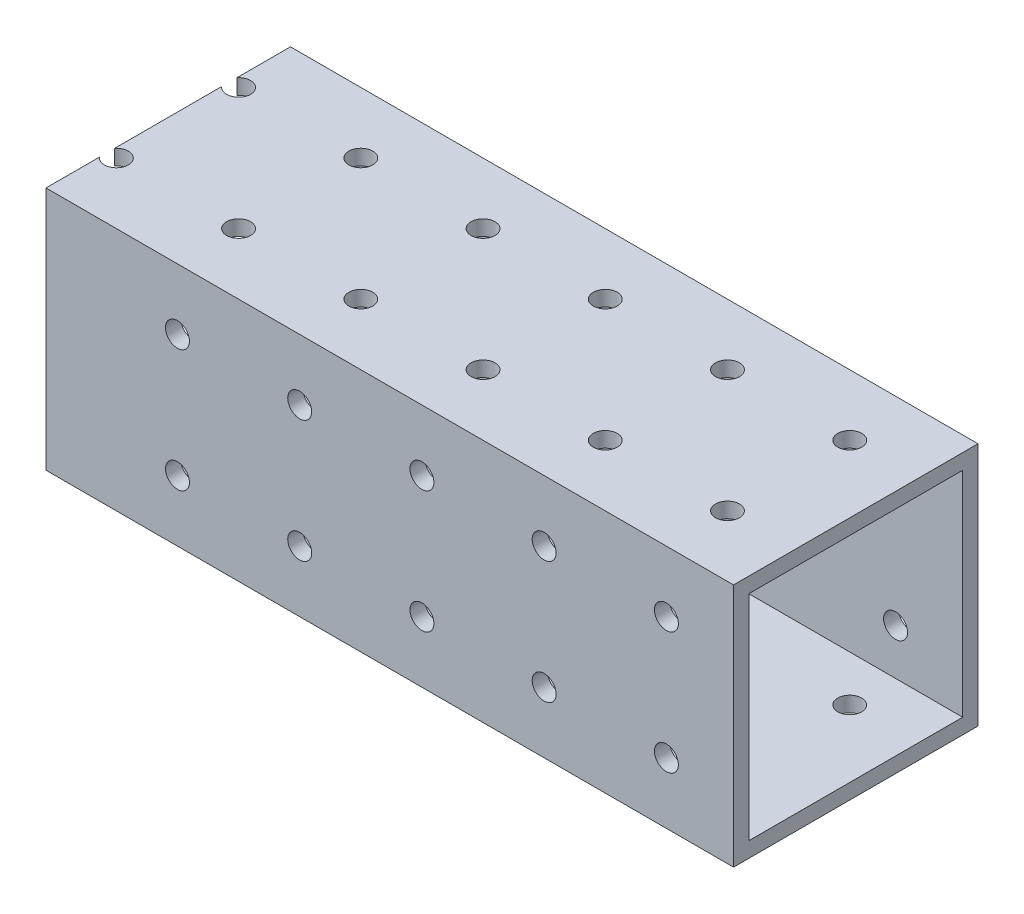
SolidWorks part; units mm, degrees
material "6061-T6 (SS)"
ref_plane "Front Plane" through (0, 0, 0) normal (0, 0, 1) x (1, 0, 0)
ref_plane "Top Plane" through (0, 0, 0) normal (0, 1, 0) x (1, 0, 0)
ref_plane "Right Plane" through (0, 0, 0) normal (1, 0, 0) x (0, 0, -1)
sketch "Sketch1" plane through (0, 0, 0) normal (1, 0, 0) x (0, 0, -1)
  line L1 (0, 0) -> (50.8, 0)
  line L2 (0, 0) -> (0, 50.8)
  line L3 (0, 50.8) -> (50.8, 50.8)
  line L4 (50.8, 0) -> (50.8, 50.8)
  dimension "D1" = 50.8
extrude "Boss-Extrude1" add sketch "Sketch1" along normal blind 142.875
shell "Shell1" thickness 3.175 removed face at (0, 25.4, -25.4) removed face at (142.875, 25.4, -25.4)
sketch "Sketch2" plane through (0, 0, -50.8) normal (0, 0, -1) x (-1, 0, 0)
  circle A0 centre (-128.9208, 38.1) radius 2.4892 construction
  circle A1 centre (-103.5208, 38.1) radius 2.4892 construction
  circle A2 centre (-78.1208, 38.1) radius 2.4892 construction
  circle A3 centre (-52.7208, 38.1) radius 2.4892 construction
  circle A4 centre (-27.3208, 38.1) radius 2.4892 construction
  circle A5 centre (-27.3208, 12.7) radius 2.4892 construction
  circle A6 centre (-52.7208, 12.7) radius 2.4892 construction
  circle A7 centre (-78.1208, 12.7) radius 2.4892 construction
  circle A8 centre (-103.5208, 12.7) radius 2.4892 construction
  circle A9 centre (-128.9208, 12.7) radius 2.4892 construction
  circle A10 centre (-128.9208, 38.1) radius 2.4892
  circle A11 centre (-103.5208, 38.1) radius 2.4892
  circle A12 centre (-78.1208, 38.1) radius 2.4892
  circle A13 centre (-52.7208, 38.1) radius 2.4892
  circle A14 centre (-27.3208, 38.1) radius 2.4892
  circle A15 centre (-27.3208, 12.7) radius 2.4892
  circle A16 centre (-52.7208, 12.7) radius 2.4892
  circle A17 centre (-78.1208, 12.7) radius 2.4892
  circle A18 centre (-103.5208, 12.7) radius 2.4892
  circle A19 centre (-128.9208, 12.7) radius 2.4892
extrude "Cut-Extrude1" cut sketch "Sketch2" against normal through all
sketch "Sketch3" plane through (0, 0, 0) normal (0, -1, 0) x (1, 0, 0)
  line L1 (128.9208, -38.1) -> (128.9208, -12.7) construction
  line L2 (128.9208, -12.7) -> (128.9208, 12.7) construction
  line L3 (287.6708, 0) -> (-309.2292, 0) construction
  line L4 (142.875, -50.8) -> (0, -50.8) construction
  circle A0 centre (128.9208, -12.7) radius 2.4892
  circle A1 centre (128.9208, -38.1) radius 2.4892
  dimension "D1" = 4.9784
  dimension "D2" = 12.7
  dimension "D3" = 12.7
extrude "Cut-Extrude2" cut sketch "Sketch3" against normal through all
pattern_linear "LPattern1" count 6 spacing 25.4 along (-1, 0, 0) of "Cut-Extrude2"
